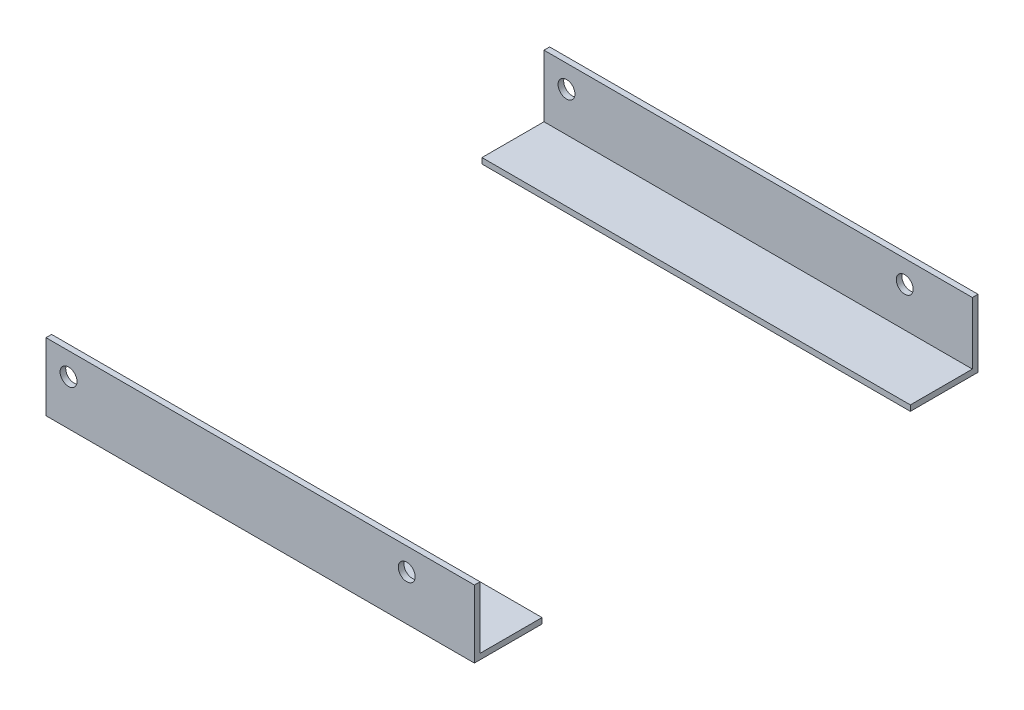
SolidWorks part; units mm, degrees
material "Plain Carbon Steel"
ref_plane "Front Plane" through (0, 0, 0) normal (0, 0, 1) x (1, 0, 0)
ref_plane "Top Plane" through (0, 0, 0) normal (0, 1, 0) x (1, 0, 0)
ref_plane "Right Plane" through (0, 0, 0) normal (1, 0, 0) x (0, 0, -1)
sketch "Sketch1" plane through (0, 0, 0) normal (0, 0, 1) x (1, 0, 0)
  line L0 (0, 0) -> (0, 38.1)
  line L1 (0, -55) -> (0, 55) construction
  line L3 (55, 0) -> (-55, 0) construction
  line L4 (38.1, 0) -> (0, 0)
  dimension "D1" = 38.1
  dimension "D2" = 38.1
extrude "Extrude-Thin1" add sketch "Sketch1" along normal mid plane 381 thin thin type one direction wall 3.175
sketch "Sketch2" plane through (0, 0, 0) normal (-1, 0, 0) x (0, 0, 1)
  line L0 (103.7336, 3.175) -> (141.8336, 3.175)
  line L2 (141.8336, 3.175) -> (141.8336, 41.275)
  line L4 (-141.8336, 3.175) -> (-141.8336, 41.275)
  line L5 (-141.8336, 3.175) -> (-103.7336, 3.175)
  line L6 (153.67, 0) -> (-153.67, 0) construction
  dimension "D1" = 141.8336
  dimension "D2" = 141.8336
  dimension "D3" = 3.175
  dimension "D4" = 38.1
extrude "Extrude-Thin2" add sketch "Sketch2" along normal blind 241.3 thin thin type one direction reverse wall 3.175
sketch "Sketch5" plane through (0, 0, 0) normal (0, 0, 1) x (1, 0, 0)
  line L0 (-241.3, 41.275) -> (-241.3, 6.35) construction
  line L1 (-241.3, 41.275) -> (0, 41.275) construction
  circle A0 centre (-228.6, 28.575) radius 4.7625
  circle A1 centre (-38.1, 28.575) radius 4.7625
  dimension "D1" = 9.525
  dimension "D2" = 12.7
  dimension "D3" = 12.7
  dimension "D4" = 190.5
extrude "Cut-Extrude3" cut sketch "Sketch5" against normal through all both and the other way through all
sketch "Sketch6" plane through (0, 0, 0) normal (0, 0, 1) x (1, 0, 0)
  line L1 (0, 41.275) -> (38.1, 41.275)
  line L2 (0, 41.275) -> (0, 0)
  line L3 (0, 0) -> (38.1, 0)
  line L4 (38.1, 41.275) -> (38.1, 0)
extrude "Cut-Extrude4" cut sketch "Sketch6" against normal through all both and the other way through all
